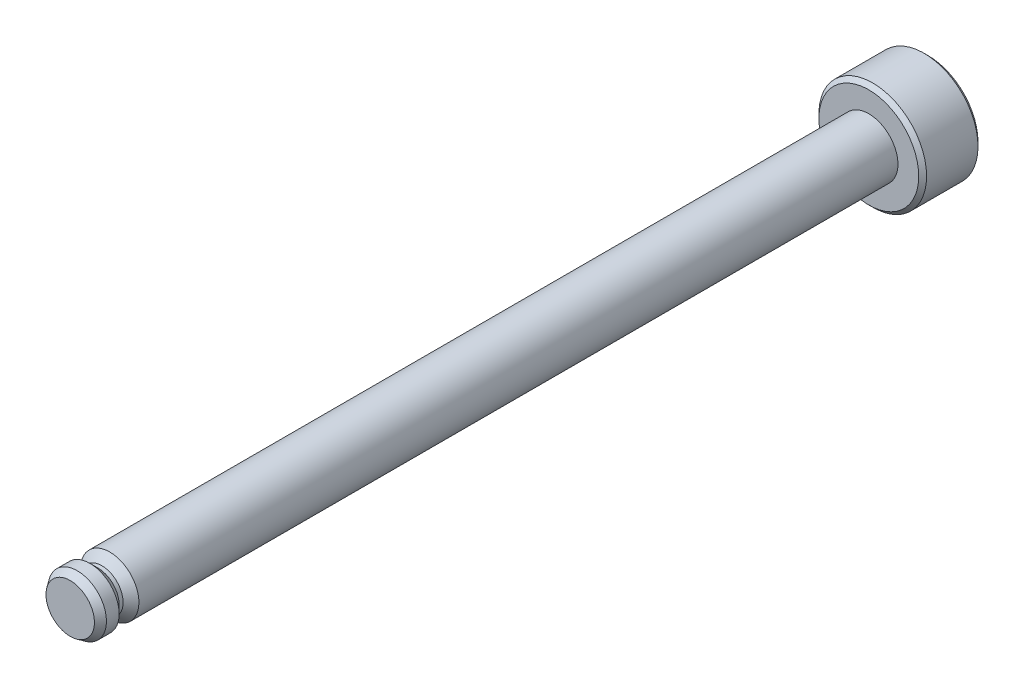
SolidWorks part; units mm, degrees
ref_plane "Front" through (0, 0, 0) normal (0, 0, 1) x (1, 0, 0)
ref_plane "Top" through (0, 0, 0) normal (0, 1, 0) x (1, 0, 0)
ref_plane "Right" through (0, 0, 0) normal (1, 0, 0) x (0, 0, -1)
sketch "Sketch2" plane through (0, 0, 0) normal (0, 0, 1) x (1, 0, 0)
  circle A0 centre (0, 0) radius 1.475
  dimension "D1" = 2.95
extrude "Shaft" add sketch "Sketch2" along normal blind 40.4
sketch "Sketch5" plane through (0, 0, 0) normal (0, 0, 1) x (1, 0, 0)
  circle A0 centre (0, 0) radius 2.725
  dimension "D1" = 5.45
extrude "Head" add sketch "Sketch5" against normal blind 3
chamfer "Chamfer1" distance 0.25 angle 55 1 edges at (1.475, 0, 40.4) first distance on face at (1.475, 0, 40.4)
chamfer "Deburs" distance 0.2 angle 45 2 edges at (2.725, 0, 0) (2.725, 0, -3)
sketch "Sketch6" plane through (0, 0, 0) normal (1, 0, 0) x (0, 0, -1)
  line L0 (0, 0) -> (-38.9, 0) construction
  line L1 (-38.9, 0) -> (-38.9, 1.075) construction
  line L2 (0, 1.475) -> (-40.043, 1.475) construction
  line L3 (-39.4, 1.475) -> (-38.4, 1.475)
  line L4 (-38.4, 1.475) -> (-38.8, 1.075)
  line L5 (-38.8, 1.075) -> (-39, 1.075)
  line L6 (-39, 1.075) -> (-39.4, 1.475)
  line L7 (-38.9, 1.075) -> (-38.9, 1.475) construction
  dimension "D1" = 38.9
  dimension "D2" = 0.4
  dimension "D3" = 1
revolve "e-Clip Notch Long" cut sketch "Sketch6" angle 360 about L0
equation "\"D1@Sketch2\"=\"Plastic Hardware OD@Box Assy.Assembly\""
equation "\"D1\"= \"Countersink Diameter@Box Assy.Assembly\" - .3mm"
equation "\"D1@Head\"=\"Countersink Depth@Box Assy.Assembly\""
equation "\"Length\"= 40mm"
equation "\"D1@Shaft\"=\"Length\"+.4mm"
equation "\"D1@Sketch6\"=\"Length\"-1.1mm"
